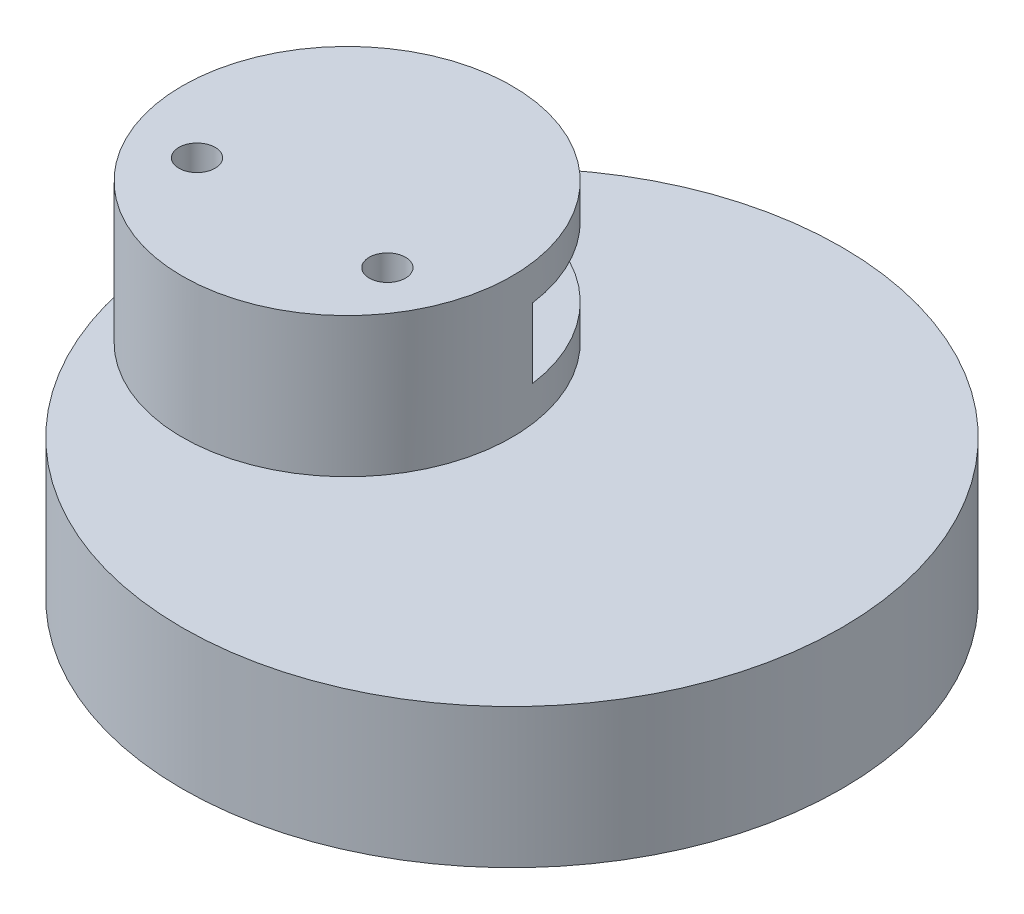
SolidWorks part; units mm, degrees
material "AISI 304"
ref_plane "Front Plane" through (0, 0, 0) normal (0, 0, 1) x (1, 0, 0)
ref_plane "Top Plane" through (0, 0, 0) normal (0, 1, 0) x (1, 0, 0)
ref_plane "Right Plane" through (0, 0, 0) normal (1, 0, 0) x (0, 0, -1)
sketch "Sketch1" plane through (0, 0, 0) normal (0, 1, 0) x (1, 0, 0)
  circle A0 centre (0, 0) radius 15
  circle A1 centre (15, 0) radius 30
  point P5 (0, 0)
  dimension "D1" = 30
  dimension "D2" = 60
  dimension "D3" = 15
extrude "Boss-Extrude1" add sketch "Sketch1" along normal blind 12.7 contours A0 region at (0, 0, 0)
extrude "Boss-Extrude2" add sketch "Sketch1<3>" against normal blind 12.7 contours A0 A1 | A0 region at (0, 0, 0) region at (20, 0, 0)
sketch "Sketch1<3>" plane through (0, 0, 0) normal (0, 1, 0) x (1, 0, 0) same geometry as "Sketch1"
sketch "Sketch2" plane through (0, 0, 0) normal (1, 0, 0) x (0, 0, -1)
  line L0 (15, 0) -> (15, 12.7) construction
  line L1 (15, 9.525) -> (2, 9.525)
  line L2 (15, 9.525) -> (15, 3.175)
  line L3 (15, 3.175) -> (2, 3.175)
  line L4 (2, 9.525) -> (2, 3.175)
  line L5 (15, 12.7) -> (-15, 12.7) construction
  line L6 (15, 0) -> (-15, 0) construction
  dimension "D1" = 2
  dimension "D2" = 3.175
  dimension "D3" = 3.175
extrude "Cut-Extrude1" cut sketch "Sketch2" against normal through all both and the other way through all
hole_wizard "M4x0.7 Tapped Hole1" positions "Sketch3" profile "Sketch4" tap size "M4x0.7" standard "ANSI Metric"
sketch "Sketch3" plane through (0, 12.7, 0) normal (0, 1, 0) x (1, 0, 0)
  line L0 (0, 10) -> (0, 0) construction
  line L1 (0, 0) -> (-8.6603, -5) construction
  line L3 (8.6603, -5) -> (0, 0) construction
  point P5 (-8.6603, -5)
  point P7 (8.6603, -5)
  dimension "D1" = 10
  dimension "D2" = 120
  dimension "D3" = 120
sketch "Sketch4" plane through (8.6603, 12.7, 5) normal (1, 0, 0) x (0, 0, 1)
  line L0 (0, 0) -> (0, 11.0914)
  line L1 (0, 11.0914) -> (1.65, 10.1)
  line L2 (1.65, 10.1) -> (1.65, 0)
  line L5 (1.65, 0) -> (0, 0)
  line L10 (0, 11.0914) -> (-1.65, 10.1) construction
  line L11 (0, -6.35) -> (0, 107.95) construction
  dimension "Tap Drill Dia." = 3.3
  dimension "Tap Drill Depth" = 10.1
  dimension "Drill Angle" = 118
cosmetic thread "Hole Thread1" parameters "D1"=8, "D2"=4
cosmetic thread "Hole Thread2" parameters "D1"=8, "D2"=4
hole_wizard "M4x0.7 Tapped Hole2" positions "Sketch5" profile "Sketch6" tap size "M4x0.7" standard "ANSI Metric"
sketch "Sketch5" plane through (0, -12.7, 0) normal (0, -1, 0) x (-1, 0, 0)
  line L0 (-15, 20) -> (-15, 0) construction
  line L1 (-15, 0) -> (-32.3205, -10) construction
  line L3 (2.3205, -10) -> (-15, 0) construction
  point P1 (-15, 20)
  point P5 (-32.3205, -10)
  point P7 (2.3205, -10)
  dimension "D1" = 120
  dimension "D2" = 120
  dimension "D3" = 20
sketch "Sketch6" plane through (15, -12.7, -20) normal (1, 0, 0) x (0, 0, -1)
  line L0 (0, 0) -> (0, 11.0914)
  line L1 (0, 11.0914) -> (1.65, 10.1)
  line L2 (1.65, 10.1) -> (1.65, 0)
  line L5 (1.65, 0) -> (0, 0)
  line L10 (0, 11.0914) -> (-1.65, 10.1) construction
  line L11 (0, -6.35) -> (0, 107.95) construction
  dimension "Tap Drill Dia." = 3.3
  dimension "Tap Drill Depth" = 10.1
  dimension "Drill Angle" = 118
cosmetic thread "Hole Thread3" parameters "D1"=8, "D2"=4
cosmetic thread "Hole Thread4" parameters "D1"=8, "D2"=4
cosmetic thread "Hole Thread5" parameters "D1"=8, "D2"=4
